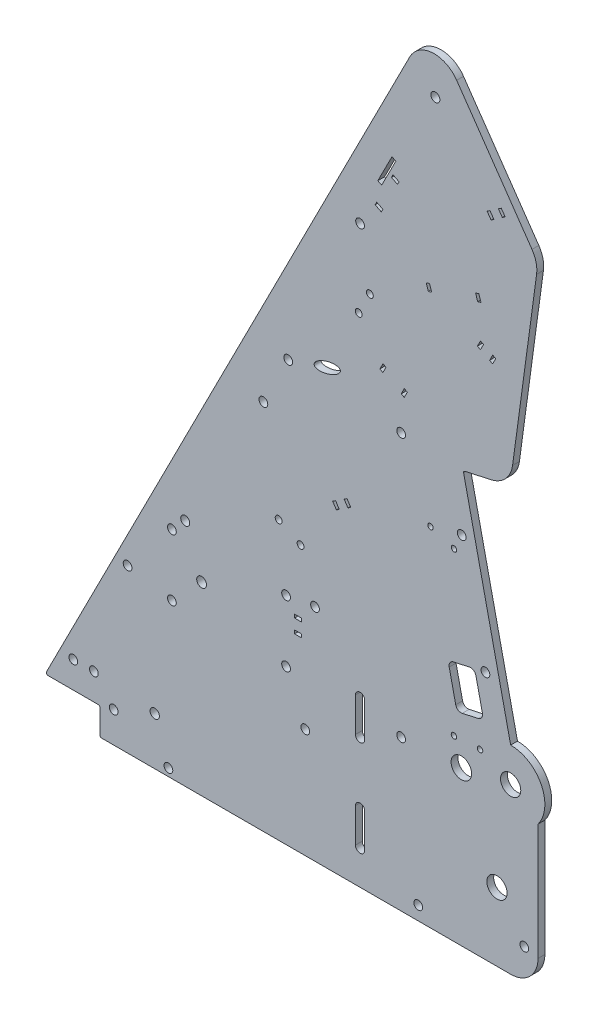
SolidWorks part; units mm, degrees
other "Markup1"
sketch "Sketch5"
ref_plane "Front Plane" through (0, 0, 0) normal (0, 0, 1) x (1, 0, 0)
ref_plane "Top Plane" through (0, 0, 0) normal (0, 1, 0) x (1, 0, 0)
ref_plane "Right Plane" through (0, 0, 0) normal (1, 0, 0) x (0, 0, -1)
sketch "Sketch1" plane through (0, 0, 0) normal (0, 0, 1) x (1, 0, 0)
  line L1 (228.6, -12.7) -> (228.6, 53.975)
  line L2 (178.7547, 351.4131) -> (0, 0)
  line L3 (228.6, 279.4) -> (178.7547, 351.4131)
  line L5 (0, 0) -> (25.4, 0)
  line L6 (25.4, 0) -> (25.4, -12.7)
  line L7 (25.4, -12.7) -> (228.6, -12.7)
  line L9 (215.9, 79.375) -> (193.9097, 178.5667)
  line L10 (193.9097, 178.5667) -> (215.6079, 183.377)
  line L11 (215.6079, 183.377) -> (228.6, 279.4)
  arc A0 (228.6, 53.975) -> (215.9, 79.375) centre (215.9, 63.5) ccw
  dimension "D7" = 12.7
  dimension "D8" = 76.2
  dimension "D10" = 31.75
  dimension "D2" = 292.1
  dimension "D3" = 25.4
  dimension "D4" = 215.9
  dimension "D5" = 394.2644
  dimension "D6" = 203.2
  dimension "D9" = 63.039
  dimension "D11" = 101.6
  dimension "D12" = 12.5
  dimension "D13" = 22.225
extrude "Boss-Extrude1" add sketch "Sketch1" along normal blind 3.175
sketch "Sketch2" plane through (0, 0, 3.175) normal (0, 0, 1) x (1, 0, 0)
  line L0 (178.7547, 351.4131) -> (0, 0) construction
  line L1 (25.4, -12.7) -> (228.6, -12.7) construction
  line L2 (215.9, 79.375) -> (193.9097, 178.5667) construction
  line L3 (193.9097, 178.5667) -> (215.6079, 183.377) construction
  line L4 (215.9, 79.375) -> (193.9097, 178.5667) construction
  line L5 (64.9432, 94.0578) -> (72.5445, 73.1732) construction
  line L6 (64.9432, 94.0578) -> (103.3734, 94.0578) construction
  line L10 (228.6, -12.7) -> (228.6, 53.975) construction
  circle A0 centre (64.9432, 94.0578) radius 2.0955
  circle A1 centre (180.975, 322.1643) radius 2.0955
  circle A2 centre (72.5445, 73.1732) radius 2.286
  circle A3 centre (193.2078, 152.3944) radius 2.032
  circle A4 centre (215.9, 63.5) radius 4.699
  circle A7 centre (173.0375, -6.35) radius 2.032
  circle A8 centre (204.203, 102.7985) radius 2.032
  circle A26 centre (209.55, 19.05) radius 4.699
  arc A30 (228.6, 53.975) -> (215.9, 79.375) centre (215.9, 63.5) ccw construction
  circle A31 centre (165.1, 179.3875) radius 2.032
  circle A35 centre (111.724, 87.4607) radius 2.032
  circle A36 centre (111.724, 58.8857) radius 2.032
  circle A37 centre (58.765, 58.8857) radius 2.032
  circle A38 centre (58.765, 87.4607) radius 2.032
  circle A39 centre (111.724, 58.8857) radius 1.905 construction
  circle A42 centre (111.724, 87.4607) radius 1.905 construction
  circle A43 centre (58.765, 58.8857) radius 1.905 construction
  circle A44 centre (58.765, 87.4607) radius 1.905 construction
  dimension "D3" = 4.191
  dimension "D5" = 4.191
  dimension "D9" = 4.572
  dimension "D20" = 9.398
  dimension "D23" = 9.398
  dimension "D18" = 4.064
  dimension "D26" = 4.064
  dimension "D14" = 4.064
  dimension "D10" = 4.064
  dimension "D2" = 15.24
  dimension "D6" = 15.24
  dimension "D7" = 22.225
  dimension "D21" = 44.45
  dimension "D22" = 6.35
  dimension "D19" = 160.3375
  dimension "D24" = 44.45
  dimension "D25" = 6.35
  dimension "D27" = 25.4
  dimension "D28" = 50.8
  dimension "D29" = 6.35
  dimension "D17" = 6.35
  dimension "D33" = 55.5625
  dimension "D15" = 114.3
  dimension "D4" = 180.975
  dimension "D8" = 70
extrude "Cut-Extrude1" cut sketch "Sketch2" against normal through all
sketch "Sketch7" plane through (0, 0, 3.175) normal (0, 0, 1) x (1, 0, 0)
  line L0 (146.05, 3.175) -> (146.05, 19.05) construction
  line L1 (143.891, 3.175) -> (143.891, 19.05)
  line L2 (148.209, 3.175) -> (148.209, 19.05)
  line L3 (146.05, 47.625) -> (146.05, 63.5) construction
  line L4 (143.891, 47.625) -> (143.891, 63.5)
  line L5 (148.209, 47.625) -> (148.209, 63.5)
  line L6 (25.4, -12.7) -> (228.6, -12.7) construction
  line L12 (228.6, -12.7) -> (228.6, 53.975) construction
  line L13 (25.4, -12.7) -> (228.6, -12.7) construction
  arc A0 (143.891, 3.175) -> (148.209, 3.175) centre (146.05, 3.175) ccw
  arc A1 (148.209, 19.05) -> (143.891, 19.05) centre (146.05, 19.05) ccw
  arc A2 (143.891, 47.625) -> (148.209, 47.625) centre (146.05, 47.625) ccw
  arc A3 (148.209, 63.5) -> (143.891, 63.5) centre (146.05, 63.5) ccw
  circle A8 centre (50.8, 9.525) radius 2.159
  point P2 (146.05, 11.1125)
  point P9 (146.05, 55.5625)
  dimension "D1" = 4.318
  dimension "D5" = 4.318
  dimension "D2" = 15.875
  dimension "D3" = 15.875
  dimension "D4" = 44.45
  dimension "D6" = 95.25
  dimension "D7" = 82.55
  dimension "D8" = 15.875
  dimension "D9" = 22.225
extrude "Cut-Extrude2" cut sketch "Sketch7" against normal through all
sketch "Sketch10" plane through (0, 0, 3.175) normal (0, 0, 1) x (1, 0, 0)
  circle A0 centre (120.65, 38.1) radius 2.032
  circle A1 centre (165.1, 57.15) radius 2.032
  circle A2 centre (13.0465, 12.3347) radius 2.032
  circle A3 centre (22.5715, 12.3347) radius 2.032
  circle A4 centre (38.2114, 62.6398) radius 2.032
  circle A5 centre (13.0465, 12.3347) radius 2.032 construction
  circle A6 centre (22.5715, 12.3347) radius 2.032 construction
  dimension "D1" = 4.064
  dimension "D3" = 38.1
  dimension "D2" = 120.65
  dimension "D4" = 63.5
  dimension "D5" = 69.85
extrude "Cut-Extrude3" cut sketch "Sketch10" against normal up to next
fillet "Fillet1" radius 12.7 4 edges at (228.6, -12.7, 1.5875) (178.7547, 351.4131, 1.5875) (215.6079, 183.377, 1.5875) (228.6, 279.4, 1.5875)
fillet "Fillet2" radius 0.7937 4 edges at (25.4, -12.7, 1.5875) (25.4, 0, 1.5875) (193.9097, 178.5667, 1.5875) (0, 0, 1.5875)
sketch "Sketch12" plane through (0, 0, 3.175) normal (0, 0, 1) x (1, 0, 0)
  circle A0 centre (31.75, 1.5875) radius 2.032
  circle A1 centre (173.0375, -6.35) radius 2.032
  circle A2 centre (222.25, 1.5875) radius 2.032
  circle A3 centre (57.15, -9.2075) radius 2.032
  circle A4 centre (57.15, -9.2075) radius 2.286 construction
  dimension "D1" = 4.064
  dimension "D2" = 4.064
extrude "Cut-Extrude5" cut sketch "Sketch12" against normal through all
sketch "Sketch13" plane through (0, 0, 3.175) normal (0, 0, 1) x (1, 0, 0)
  line L1 (228.6, 0) -> (228.6, 53.975) construction
  line L2 (1.2943, 0) -> (24.6062, 0) construction
  line L3 (26.1937, -12.7) -> (215.9, -12.7) construction
  line L8 (178.2697, 245.9923) -> (176.7582, 245.5069)
  line L9 (179.2404, 242.9693) -> (178.2697, 245.9923)
  line L10 (177.7289, 242.4839) -> (179.2404, 242.9693)
  line L11 (176.7582, 245.5069) -> (177.7289, 242.4839)
  line L12 (178.2697, 245.9923) -> (176.7582, 245.5069)
  line L13 (179.2404, 242.9693) -> (178.2697, 245.9923)
  line L14 (177.7289, 242.4839) -> (179.2404, 242.9693)
  line L15 (176.7582, 245.5069) -> (177.7289, 242.4839)
  line L16 (160.8477, 288.1984) -> (154.2836, 275.294)
  line L17 (200.6096, 249.8308) -> (202.1211, 250.3161)
  line L18 (199.639, 252.8538) -> (200.6096, 249.8308)
  line L19 (201.1505, 253.3391) -> (199.639, 252.8538)
  line L20 (202.1211, 250.3161) -> (201.1505, 253.3391)
  line L21 (200.6096, 249.8308) -> (202.1211, 250.3161)
  line L22 (199.639, 252.8538) -> (200.6096, 249.8308)
  line L23 (201.1505, 253.3391) -> (199.639, 252.8538)
  line L24 (202.1211, 250.3161) -> (201.1505, 253.3391)
  line L25 (160.8477, 288.1984) -> (162.6303, 287.2917)
  line L26 (160.5905, 279.7801) -> (163.4204, 278.3406)
  line L27 (161.3102, 281.1951) -> (160.5905, 279.7801)
  line L28 (164.1402, 279.7556) -> (161.3102, 281.1951)
  line L29 (163.4204, 278.3406) -> (164.1402, 279.7556)
  line L30 (160.5905, 279.7801) -> (163.4204, 278.3406)
  line L31 (161.3102, 281.1951) -> (160.5905, 279.7801)
  line L32 (164.1402, 279.7556) -> (161.3102, 281.1951)
  line L33 (163.4204, 278.3406) -> (164.1402, 279.7556)
  line L34 (154.2836, 275.294) -> (156.0662, 274.3872)
  line L35 (162.6303, 287.2917) -> (156.0662, 274.3872)
  line L36 (153.7897, 266.4104) -> (153.0699, 264.9954)
  line L37 (156.6196, 264.9709) -> (153.7897, 266.4104)
  line L38 (155.8998, 263.5559) -> (156.6196, 264.9709)
  line L39 (153.0699, 264.9954) -> (155.8998, 263.5559)
  line L40 (153.7897, 266.4104) -> (153.0699, 264.9954)
  line L41 (156.6196, 264.9709) -> (153.7897, 266.4104)
  line L42 (155.8998, 263.5559) -> (156.6196, 264.9709)
  line L43 (153.0699, 264.9954) -> (155.8998, 263.5559)
  line L110 (153.9925, 274.7218) -> (157.3929, 281.4066) construction
  line L111 (155.7751, 273.815) -> (159.1755, 280.4999) construction
  line L122 (203.3303, 234.0299) -> (201.9154, 234.7497)
  line L123 (201.8908, 231.2) -> (203.3303, 234.0299)
  line L124 (200.4759, 231.9198) -> (201.8908, 231.2)
  line L125 (201.9154, 234.7497) -> (200.4759, 231.9198)
  line L126 (203.3303, 234.0299) -> (201.9154, 234.7497)
  line L127 (201.8908, 231.2) -> (203.3303, 234.0299)
  line L128 (200.4759, 231.9198) -> (201.8908, 231.2)
  line L129 (201.9154, 234.7497) -> (200.4759, 231.9198)
  line L130 (206.1357, 229.0407) -> (207.5507, 228.321)
  line L131 (207.5752, 231.8707) -> (206.1357, 229.0407)
  line L132 (208.9902, 231.1509) -> (207.5752, 231.8707)
  line L133 (207.5507, 228.321) -> (208.9902, 231.1509)
  line L134 (206.1357, 229.0407) -> (207.5507, 228.321)
  line L135 (207.5752, 231.8707) -> (206.1357, 229.0407)
  line L136 (208.9902, 231.1509) -> (207.5752, 231.8707)
  line L137 (207.5507, 228.321) -> (208.9902, 231.1509)
  line L138 (211.5405, 292.889) -> (210.2352, 291.9855)
  line L139 (213.3475, 290.2784) -> (211.5405, 292.889)
  line L140 (212.0422, 289.3749) -> (213.3475, 290.2784)
  line L141 (210.2352, 291.9855) -> (212.0422, 289.3749)
  line L142 (211.5405, 292.889) -> (210.2352, 291.9855)
  line L143 (213.3475, 290.2784) -> (211.5405, 292.889)
  line L144 (212.0422, 289.3749) -> (213.3475, 290.2784)
  line L145 (210.2352, 291.9855) -> (212.0422, 289.3749)
  line L146 (206.3193, 289.275) -> (205.014, 288.3715)
  line L147 (208.1263, 286.6644) -> (206.3193, 289.275)
  line L148 (206.821, 285.7609) -> (208.1263, 286.6644)
  line L149 (205.014, 288.3715) -> (206.821, 285.7609)
  line L150 (206.3193, 289.275) -> (205.014, 288.3715)
  line L151 (208.1263, 286.6644) -> (206.3193, 289.275)
  line L152 (206.821, 285.7609) -> (208.1263, 286.6644)
  line L153 (205.014, 288.3715) -> (206.821, 285.7609)
  line L184 (133.3504, 136.102) -> (135.0815, 133.4404)
  line L185 (133.3504, 136.102) -> (134.6812, 136.9675)
  line L186 (135.0815, 133.4404) -> (136.4123, 134.3059)
  line L187 (155.2281, 200.1197) -> (156.643, 199.3999)
  line L188 (156.6676, 202.9496) -> (155.2281, 200.1197)
  line L189 (158.0826, 202.2298) -> (156.6676, 202.9496)
  line L190 (156.643, 199.3999) -> (158.0826, 202.2298)
  line L191 (155.2281, 200.1197) -> (156.643, 199.3999)
  line L192 (156.6676, 202.9496) -> (155.2281, 200.1197)
  line L193 (158.0826, 202.2298) -> (156.6676, 202.9496)
  line L194 (156.643, 199.3999) -> (158.0826, 202.2298)
  line L195 (134.6812, 136.9675) -> (136.4123, 134.3059)
  line L196 (165.1328, 195.0814) -> (166.5478, 194.3617)
  line L197 (166.5723, 197.9113) -> (165.1328, 195.0814)
  line L198 (167.9873, 197.1916) -> (166.5723, 197.9113)
  line L199 (166.5478, 194.3617) -> (167.9873, 197.1916)
  line L200 (165.1328, 195.0814) -> (166.5478, 194.3617)
  line L201 (166.5723, 197.9113) -> (165.1328, 195.0814)
  line L202 (167.9873, 197.1916) -> (166.5723, 197.9113)
  line L203 (166.5478, 194.3617) -> (167.9873, 197.1916)
  line L204 (140.4047, 136.9025) -> (138.6737, 139.5641)
  line L205 (140.4047, 136.9025) -> (141.7355, 137.768)
  line L206 (138.6737, 139.5641) -> (140.0045, 140.4296)
  line L207 (141.7355, 137.768) -> (140.0045, 140.4296)
  line L209 (169.1053, 332.4434) -> (0.5868, 1.1536) construction
  line L210 (88.0466, 102.1523) -> (85.2167, 103.5918) construction
  line L288 (115.661, 81.8727) -> (118.836, 81.8727)
  line L289 (115.661, 81.8727) -> (115.661, 80.2852)
  line L290 (118.836, 81.8727) -> (118.836, 80.2852)
  line L291 (115.661, 80.2852) -> (118.836, 80.2852)
  line L292 (115.661, 75.5227) -> (118.836, 75.5227)
  line L293 (115.661, 75.5227) -> (115.661, 73.9352)
  line L294 (118.836, 75.5227) -> (118.836, 73.9352)
  line L295 (115.661, 73.9352) -> (118.836, 73.9352)
  line L297 (115.661, 86.2542) -> (115.661, 60.0922) construction
  line L298 (59.9715, 91.3977) -> (110.5175, 91.3977) construction
  circle A0 centre (112.7125, 182.5625) radius 2.032
  circle A1 centre (146.05, 254) radius 2.032
  circle A2 centre (101.1964, 159.9231) radius 2.032 construction
  circle A3 centre (101.1964, 159.9231) radius 2.032
  circle A4 centre (145.4254, 217.7376) radius 1.6 construction
  circle A5 centre (150.594, 227.8985) radius 1.6 construction
  circle A7 centre (145.4254, 217.7376) radius 1.6
  circle A8 centre (150.594, 227.8985) radius 1.6
  circle A9 centre (108.294, 116.1502) radius 1.6 construction
  circle A10 centre (118.455, 110.9816) radius 1.6 construction
  circle A11 centre (108.294, 116.1502) radius 1.6
  circle A12 centre (118.455, 110.9816) radius 1.6
  ellipse E0 centre (130.8261, 188.4615) end of major axis (136.864, 190.4279) minor radius 2.3812 construction
  ellipse E1 centre (130.8261, 188.4615) end of major axis (136.864, 190.4279) minor radius 2.3812
  dimension "D2" = 4.064
  dimension "D5" = 4.064
  dimension "D1" = 195.2625
  dimension "D3" = 82.55
  dimension "D4" = 254
  dimension "D6" = 115.8875
  dimension "D11" = 7.62
  dimension "D12" = 6.858
  dimension "D13" = 1.5875
  dimension "D14" = 3.175
  dimension "D15" = 4.7625
  dimension "D16" = 60
  dimension "D17" = 57.15
  dimension "D24" = 50.8
  dimension "D29" = 3.175
  dimension "D30" = 1.5875
  dimension "D31" = 4.7625
  dimension "D32" = 0
  dimension "D33" = 9.525
  dimension "D7" = 0
  dimension "D8" = 0
  dimension "D9" = 0
  dimension "D10" = 0
  dimension "D18" = 0
  dimension "D19" = 0
  dimension "D20" = 0
  dimension "D21" = 0
  dimension "D22" = 0
  dimension "D23" = 0
extrude "Cut-Extrude6" cut sketch "Sketch13" against normal through all
sketch "Sketch14" plane through (0, 0, 3.175) normal (0, 0, 1) x (1, 0, 0)
  line L5 (186.8444, 98.9502) -> (199.2434, 101.699)
  line L6 (186.8444, 98.9502) -> (190.9676, 80.3518)
  line L7 (190.9676, 80.3518) -> (203.3665, 83.1006)
  line L8 (199.2434, 101.699) -> (203.3665, 83.1006)
  line L14 (202.8168, 85.5804) -> (199.7931, 99.2192) construction
  line L15 (193.4474, 80.9015) -> (200.8868, 82.5508) construction
  line L16 (187.3942, 96.4704) -> (190.4178, 82.8316) construction
  line L17 (196.7636, 101.1493) -> (189.3242, 99.5) construction
  circle A0 centre (189.6022, 69.9806) radius 1.27
  circle A1 centre (201.7089, 70.5092) radius 1.27
  circle A2 centre (189.6022, 69.9806) radius 1.27 construction
  circle A3 centre (201.7089, 70.5092) radius 1.27 construction
  circle A4 centre (165.1, 57.15) radius 2.032
  circle A5 centre (125.1498, 89.5229) radius 2.032
  circle A6 centre (178.7216, 148.5324) radius 1.27
  circle A8 centre (178.7216, 148.5324) radius 1.27 construction
  circle A9 centre (189.6226, 145.0954) radius 1.27
  circle A10 centre (189.6226, 145.0954) radius 1.27 construction
  point P8 (152.4, 88.9)
  dimension "D1" = 4.064
extrude "Cut-Extrude7" cut sketch "Sketch14" against normal through all both and the other way through all
fillet "Fillet3" radius 2.54 4 edges at (199.2434, 101.699, 1.5875) (186.8444, 98.9502, 1.5875) (190.9676, 80.3518, 1.5875) (203.3665, 83.1006, 1.5875)
sketch "Sketch15" plane through (0, 0, 3.175) normal (0, 0, 1) x (1, 0, 0)
  circle A0 centre (193.04, 58.801) radius 4.7625 construction
  circle A1 centre (193.04, 58.801) radius 4.7625
extrude "Cut-Extrude8" cut sketch "Sketch15" against normal through all
equation "\"D6@Sketch2\"=\"D2@Sketch2\""
